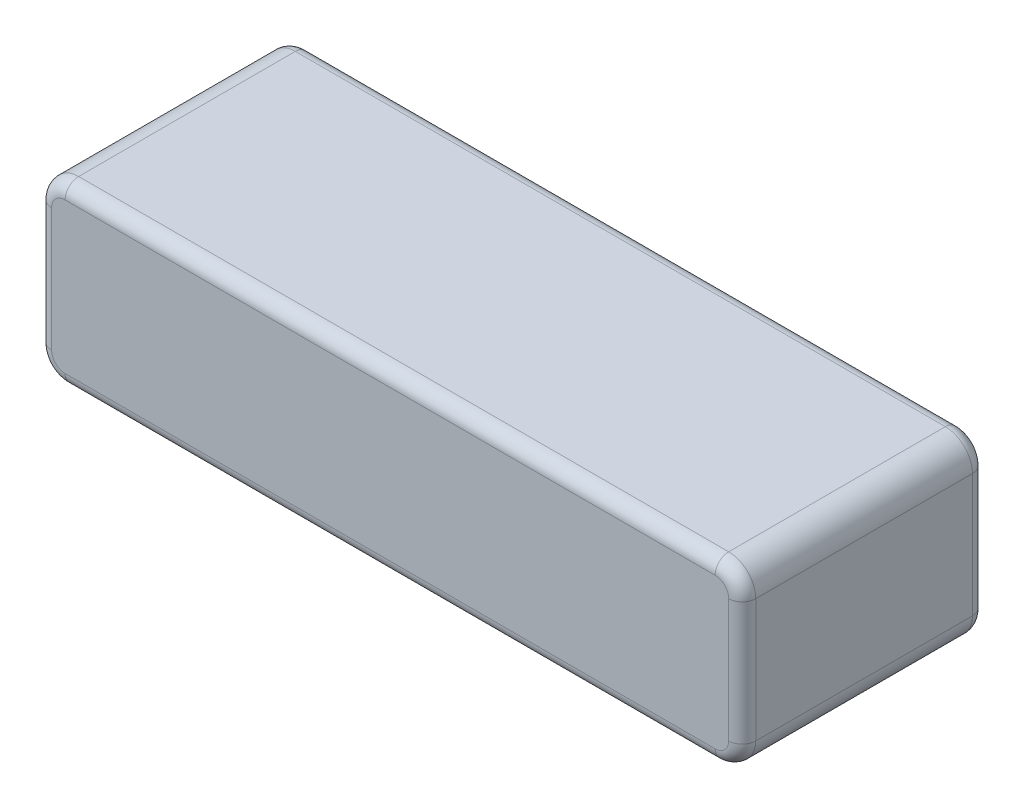
SolidWorks part; units mm, degrees
material "Custom Plastic"
ref_plane "Front Plane" through (0, 0, 0) normal (0, 0, 1) x (1, 0, 0)
ref_plane "Top Plane" through (0, 0, 0) normal (0, 1, 0) x (1, 0, 0)
ref_plane "Right Plane" through (0, 0, 0) normal (1, 0, 0) x (0, 0, -1)
sketch "Sketch1" plane through (0, 0, 0) normal (0, 1, 0) x (1, 0, 0)
  line L1 (-26, -9) -> (26, -9)
  line L2 (-26, -9) -> (-26, 9)
  line L3 (-26, 9) -> (26, 9)
  line L4 (26, -9) -> (26, 9)
  line L5 (-26, -9) -> (26, 9) construction
  line L6 (-26, 9) -> (26, -9) construction
  point P0 (0, 0)
  dimension "D1" = 52
  dimension "D2" = 18
extrude "Boss-Extrude1" add sketch "Sketch1" along normal blind 13.1
fillet "Fillet1" radius 2 4 edges at (-26, 0, 0) (-26, 13.1, 0) (26, 0, 0) (26, 13.1, 0)
fillet "Fillet2" radius 1 16 edges at (-25.4142, 12.5142, 9) (-26, 6.55, 9) (-25.4142, 0.5858, 9) (0, 0, 9) (25.4142, 0.5858, 9) (26, 6.55, 9) (25.4142, 12.5142, 9) (25.4142, 12.5142, -9) (26, 6.55, -9) (25.4142, 0.5858, -9) (0, 0, -9) (-25.4142, 0.5858, -9) (-26, 6.55, -9) (-25.4142, 12.5142, -9) (0, 13.1, 9) (0, 13.1, -9)
